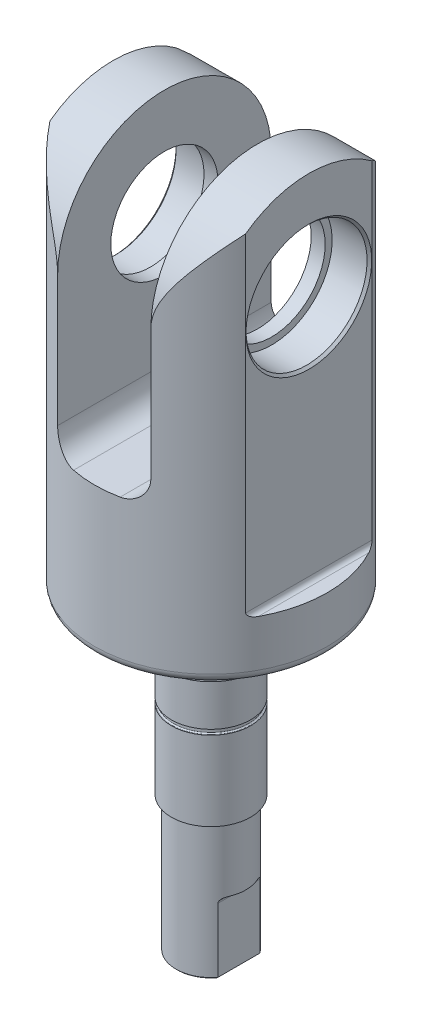
SolidWorks part; units mm, degrees
material "3.3547 (EN-AW 5083)"
ref_plane "Front Plane" through (0, 0, 0) normal (0, 0, 1) x (1, 0, 0)
ref_plane "Top Plane" through (0, 0, 0) normal (0, 1, 0) x (1, 0, 0)
ref_plane "Right Plane" through (0, 0, 0) normal (1, 0, 0) x (0, 0, -1)
sketch "Sketch1" plane through (0, 0, 0) normal (0, 1, 0) x (1, 0, 0)
  arc A0 (17.0833, 18.2527) -> (17.0833, -18.2527) centre (0, 0) ccw
  arc A1 (17.0833, -18.2527) -> (17.0833, 18.2527) centre (0, 0) ccw
  dimension "D1" = 25
extrude "Boss-Extrude1" add sketch "Sketch1" along normal blind 12
sketch "Sketch2" plane through (0, 12, 0) normal (0, 1, 0) x (1, 0, 0)
  line L0 (-44.2539, 0) -> (44.2539, 0) construction
  line L1 (-21, -25) -> (-10, -25)
  line L2 (-21, -25) -> (-21, 25)
  line L3 (-21, 25) -> (-10, 25)
  line L4 (-10, -25) -> (-10, 25)
  line L5 (-21, -25) -> (-10, 25) construction
  line L6 (-21, 25) -> (-10, -25) construction
  line L7 (0, -44.7868) -> (0, 44.7868) construction
  line L8 (10, -25) -> (21, -25)
  line L9 (10, -25) -> (10, 25)
  line L10 (10, 25) -> (21, 25)
  line L11 (21, -25) -> (21, 25)
  line L12 (10, -25) -> (21, 25) construction
  line L13 (10, 25) -> (21, -25) construction
  point P0 (-15.5, 0)
  point P7 (15.5, 0)
  dimension "D1" = 20
  dimension "D2" = 11
  dimension "D3" = 50
  dimension "D4" = 10
  dimension "D5" = 11
extrude "Boss-Extrude2" add sketch "Sketch2" along normal blind 80
fillet "Fillet1" radius 10 4 edges at (15.5, 92, -25) (15.5, 92, 25) (-15.5, 92, -25) (-15.5, 92, 25)
sketch "Sketch9" plane through (0, 0, 0) normal (0, 1, 0) x (1, 0, 0)
  circle A0 centre (0, 0) radius 25
  circle A1 centre (0, 0) radius 35.5279
  dimension "D1" = 50
extrude "Cut-Extrude5" cut sketch "Sketch9" against normal through all both and the other way through all
sketch "Sketch4" plane through (-21, 0, 0) normal (-1, 0, 0) x (0, 0, 1)
  line L0 (0, -44.2539) -> (0, 44.2539) construction
  line L2 (-22.9129, 65) -> (-31.155, 65)
  line L3 (-31.155, 65) -> (-31.155, 113.2536)
  line L4 (-31.155, 113.2536) -> (29.5344, 113.2536)
  line L5 (29.5344, 113.2536) -> (29.5344, 65)
  line L6 (29.5344, 65) -> (22.9129, 65)
  line L7 (-25, 0) -> (25, 0) construction
  arc A1 (22.9129, 65) -> (-22.9129, 65) centre (0, 65) ccw
  dimension "D1" = 22.9129
  dimension "D2" = 65
extrude "Cut-Extrude1" cut sketch "Sketch4" against normal blind 50
sketch "Sketch6" plane through (0, 12, 0) normal (0, 1, 0) x (1, 0, 0)
  line L6 (-10, -22.9129) -> (-10, 22.9129)
  line L8 (10, -22.9129) -> (10, 22.9129)
  arc A2 (-10, -22.9129) -> (10, -22.9129) centre (0, 0) ccw
  arc A3 (-10, -22.9129) -> (10, -22.9129) centre (0, 0) ccw
  arc A4 (10, 22.9129) -> (-10, 22.9129) centre (0, 0) ccw
  arc A5 (10, 22.9129) -> (-10, 22.9129) centre (0, 0) ccw
  point P0 (0, 0)
extrude "Boss-Extrude3" add sketch "Sketch6" along normal blind 20 contours L8 A4 L6 A2 region at (0, 12, 0)
sketch "Sketch8" plane through (-21, 0, 0) normal (-1, 0, 0) x (0, 0, 1)
  line L0 (0, -44.2539) -> (0, 44.2539) construction
  line L2 (55, 0) -> (-55, 0) construction
  circle A0 centre (-11, 20) radius 1
  circle A1 centre (0, 20) radius 1
  circle A2 centre (11, 20) radius 1
  dimension "D1" = 11
  dimension "D3" = 2
  dimension "D2" = 11
  dimension "D4" = 20
extrude "Cut-Extrude4" cut sketch "Sketch8" against normal blind 5
fillet "Fillet5" radius 1 2 edges at (21, 12, 0) (-21, 12, 0)
fillet "Fillet6" radius 5 2 edges at (10, 32, 0) (-10, 32, 0)
sketch "Sketch10" plane through (-21, 0, 0) normal (-1, 0, 0) x (0, 0, 1)
  circle A0 centre (0, 65) radius 11.5
  dimension "D1" = 23
  dimension "D2" = 65
extrude "Cut-Extrude6" cut sketch "Sketch10" against normal through all
sketch "Sketch11" plane through (-21, 0, 0) normal (-1, 0, 0) x (0, 0, 1)
  circle A0 centre (0, 65) radius 13
  dimension "D1" = 26
extrude "Cut-Extrude7" cut sketch "Sketch11" against normal blind 8
mirror "Mirror1" about plane through (0, 0, 0) normal (1, 0, 0) of "Cut-Extrude7"
sketch "Sketch12" plane through (0, 0, 0) normal (1, 0, 0) x (0, 0, -1)
  line L0 (55, 0) -> (-55, 0) construction
  line L2 (-10, 0) -> (0, 0)
  line L3 (-10, 0) -> (-10, -10)
  line L4 (-10, -10) -> (-8.5, -10)
  line L5 (-8.5, -10) -> (-8.5, -19.9)
  line L8 (-7.5, -67) -> (0, -67)
  line L9 (0, 12.112) -> (0, -93.8197) construction
  line L10 (0, 44.2539) -> (0, -44.2539) construction
  line L11 (0, -67) -> (0, 0)
  line L15 (-7.5, -38) -> (-7.5, -67)
  line L16 (-8.5, -38) -> (-7.5, -38)
  line L17 (-8.5, -19.9) -> (-8.1, -19.9)
  line L18 (-8.1, -19.9) -> (-8.1, -21)
  line L19 (-8.1, -21) -> (-8.5, -21)
  line L20 (-8.5, -21) -> (-8.5, -38)
  dimension "D1" = 7.5
  dimension "D2" = 8.5
  dimension "D3" = 10
  dimension "D4" = 10
  dimension "D5" = 28
  dimension "D6" = 1.1
  dimension "D7" = 8.1
  dimension "D8" = 29
  dimension "D9" = 11
revolve "Revolve1" add sketch "Sketch12" angle 360 about L9
fillet "Fillet7" radius 2 1 edges at (0, 0, 25)
fillet "Fillet8" radius 0.25 4 edges at (0, -38, 7.5) (0, -10, 8.5) (0, -21, 8.1) (0, -19.9, 8.1)
sketch "Sketch13" plane through (0, -67, 0) normal (0, -1, 0) x (1, 0, 0)
  line L2 (-6, -4.5) -> (-6, 4.5)
  line L4 (6, -4.5) -> (6, 4.5)
  arc A0 (-6, 4.5) -> (-6, -4.5) centre (0, 0) ccw
  arc A2 (6, -4.5) -> (6, 4.5) centre (0, 0) ccw
  circle A4 centre (0, 0) radius 7.5 construction
  dimension "D1" = 12
extrude "Cut-Extrude8" cut sketch "Sketch13" against normal blind 15
fillet "Fillet9" radius 1 2 edges at (6, -52, 0) (-6, -52, 0)
fillet "Fillet10" radius 5 1 edges at (0, 0, 10)
chamfer "Chamfer1" distance 0.25 angle 45 4 edges at (-6, -67, 0) (0, -67, -7.5) (0, -67, 7.5) (6, -67, 0)
sketch "Sketch18" plane through (-21, 0, 0) normal (-1, 0, 0) x (0, 0, 1)
  point P0 (-11, 20)
  point P3 (11, 20)
hole_wizard "Ø4.0mm Dowel Hole1" positions "Sketch18" profile "Sketch19" hole size "Ø4.0" standard "ANSI Metric"
sketch "Sketch19" plane through (-21, 20, -11) normal (0, 1, 0) x (0, 0, 1)
  line L0 (0, 0) -> (0, 21.2017)
  line L1 (0, 21.2017) -> (2, 20)
  line L2 (2, 20) -> (2, 0)
  line L5 (2, 0) -> (0, 0)
  line L10 (0, 21.2017) -> (-2, 20) construction
  line L11 (0, -6.35) -> (0, 107.95) construction
  dimension "Hole Dia." = 4
  dimension "Hole Depth" = 20
  dimension "Drill Angle" = 118
sketch "Sketch22" plane through (-21, 0, 0) normal (-1, 0, 0) x (0, 0, 1)
  point P0 (0, 20)
hole_wizard "M4x0.7 Tapped Hole1" positions "Sketch22" profile "Sketch21" tap size "M4x0.7" standard "ANSI Metric"
sketch "Sketch21" plane through (-21, 20, 0) normal (0, 1, 0) x (0, 0, 1)
  line L0 (0, 0) -> (0, 12.4914)
  line L1 (0, 12.4914) -> (1.65, 11.5)
  line L2 (1.65, 11.5) -> (1.65, 0)
  line L5 (1.65, 0) -> (0, 0)
  line L10 (0, 12.4914) -> (-1.65, 11.5) construction
  line L11 (0, -6.35) -> (0, 107.95) construction
  dimension "Tap Drill Dia." = 3.3
  dimension "Tap Drill Depth" = 11.5
  dimension "Drill Angle" = 118
cosmetic thread "Hole Thread1" parameters "D1"=8, "D2"=4
chamfer "Chamfer2" distance 0.5 angle 45 2 edges at (21, 65, 13) (-21, 65, 13)
sketch "Sketch14" plane through (5, 0, 0) normal (1, 0, 0) x (0, 0, -1)
  line L0 (-21.527, -48.25) -> (25.6585, -48.25) construction
  line L1 (7.5, -39.25) -> (-7.5, -39.25) construction
  line L2 (-16.9006, -48.25) -> (15.606, -48.25)
  dimension "D1" = 9
split line "Split Line1"
sketch "Sketch15" plane through (5, 0, 0) normal (1, 0, 0) x (0, 0, -1)
  line L0 (-16.6755, -51.75) -> (21.2078, -51.75)
  line L1 (-5.5902, -63.75) -> (5.5902, -63.75) construction
  dimension "D1" = 12
split line "Split Line4"
